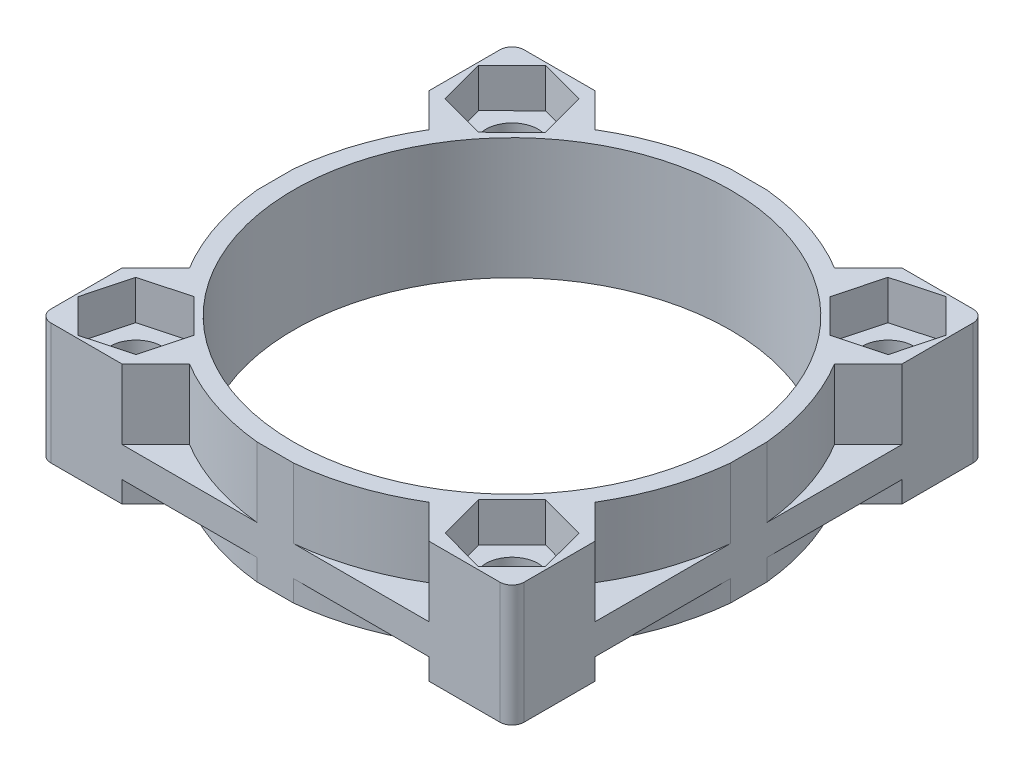
SolidWorks part; units mm, degrees
ref_plane "Front Plane" through (0, 0, 0) normal (0, 0, 1) x (1, 0, 0)
ref_plane "Top Plane" through (0, 0, 0) normal (0, 1, 0) x (1, 0, 0)
ref_plane "Right Plane" through (0, 0, 0) normal (1, 0, 0) x (0, 0, -1)
ref_plane "Plane1" through (0, 35.3803, 0) normal (0, -1, 0) x (1, 0, 0)
sketch "Sketch1" plane through (0, 35.3803, 0) normal (0, -1, 0) x (1, 0, 0)
  line L0 (498.5578, 781.9917) -> (537.5578, 781.9917)
  line L1 (537.5578, 781.9917) -> (537.5578, 820.9917)
  line L2 (537.5578, 820.9917) -> (498.5578, 820.9917)
  line L3 (498.5578, 820.9917) -> (498.5578, 781.9917)
extrude "Boss-Extrude1" add sketch "Sketch1" against normal blind 10
sketch "Sketch2" plane through (0, 45.3803, 0) normal (0, 1, 0) x (-1, 0, 0)
  line L0 (-505.3955, 781.9917) -> (-508.1811, 784.7774)
  line L1 (-516.5553, 781.9917) -> (-505.3955, 781.9917)
  arc A0 (-508.1811, 784.7774) -> (-516.5553, 781.9917) centre (-518.5578, 801.9917) cw
extrude "Cut-Extrude1" cut sketch "Sketch2" against normal blind 5.75
sketch "Sketch3" plane through (0, 35.3803, 0) normal (0, -1, 0) x (1, 0, 0)
  line L0 (508.1811, 784.7774) -> (505.3955, 781.9917)
  line L1 (505.3955, 781.9917) -> (516.5553, 781.9917)
  arc A0 (516.5553, 781.9917) -> (508.1811, 784.7774) centre (518.5578, 801.9917) cw
extrude "Cut-Extrude2" cut sketch "Sketch3" against normal blind 1.75
sketch "Sketch4" plane through (0, 35.3803, 0) normal (0, -1, 0) x (1, 0, 0)
  line L0 (530.7201, 781.9917) -> (527.9344, 784.7774)
  line L1 (519.5603, 781.9917) -> (530.7201, 781.9917)
  arc A0 (527.9344, 784.7774) -> (519.5603, 781.9917) centre (517.5578, 801.9917) cw
extrude "Cut-Extrude3" cut sketch "Sketch4" against normal blind 1.75
sketch "Sketch5" plane through (0, 45.3803, 0) normal (0, 1, 0) x (-1, 0, 0)
  line L0 (-527.9344, 784.7774) -> (-530.7201, 781.9917)
  line L1 (-530.7201, 781.9917) -> (-519.5603, 781.9917)
  arc A0 (-519.5603, 781.9917) -> (-527.9344, 784.7774) centre (-517.5578, 801.9917) cw
extrude "Cut-Extrude4" cut sketch "Sketch5" against normal blind 5.75
sketch "Sketch6" plane through (0, 35.3803, 0) normal (0, -1, 0) x (1, 0, 0)
  line L0 (498.5578, 788.8295) -> (501.3434, 791.6151)
  line L1 (498.5578, 799.9892) -> (498.5578, 788.8295)
  arc A0 (501.3434, 791.6151) -> (498.5578, 799.9892) centre (518.5578, 801.9917) cw
extrude "Cut-Extrude5" cut sketch "Sketch6" against normal blind 1.75
sketch "Sketch7" plane through (0, 45.3803, 0) normal (0, 1, 0) x (-1, 0, 0)
  line L0 (-501.3434, 791.6151) -> (-498.5578, 788.8295)
  line L1 (-498.5578, 788.8295) -> (-498.5578, 799.9892)
  arc A0 (-498.5578, 799.9892) -> (-501.3434, 791.6151) centre (-518.5578, 801.9917) cw
extrude "Cut-Extrude6" cut sketch "Sketch7" against normal blind 5.75
sketch "Sketch8" plane through (0, 45.3803, 0) normal (0, 1, 0) x (-1, 0, 0)
  line L0 (-498.5578, 814.154) -> (-501.3305, 811.3471)
  line L1 (-498.5578, 802.9942) -> (-498.5578, 814.154)
  arc A0 (-501.3305, 811.3471) -> (-498.5578, 802.9942) centre (-518.5578, 800.9917) cw
extrude "Cut-Extrude7" cut sketch "Sketch8" against normal blind 5.75
sketch "Sketch9" plane through (0, 35.3803, 0) normal (0, -1, 0) x (1, 0, 0)
  line L0 (501.3305, 811.3471) -> (498.5578, 814.154)
  line L1 (498.5578, 814.154) -> (498.5578, 802.9942)
  arc A0 (498.5578, 802.9942) -> (501.3305, 811.3471) centre (518.5578, 800.9917) cw
extrude "Cut-Extrude8" cut sketch "Sketch9" against normal blind 1.75
sketch "Sketch10" plane through (0, 35.3803, 0) normal (0, -1, 0) x (1, 0, 0)
  line L0 (505.3955, 820.9917) -> (508.1811, 818.2061)
  line L1 (516.5553, 820.9917) -> (505.3955, 820.9917)
  arc A0 (508.1811, 818.2061) -> (516.5553, 820.9917) centre (518.5578, 800.9917) cw
extrude "Cut-Extrude9" cut sketch "Sketch10" against normal blind 1.75
sketch "Sketch11" plane through (0, 45.3803, 0) normal (0, 1, 0) x (-1, 0, 0)
  line L0 (-508.1811, 818.2061) -> (-505.3955, 820.9917)
  line L1 (-505.3955, 820.9917) -> (-516.5553, 820.9917)
  arc A0 (-516.5553, 820.9917) -> (-508.1811, 818.2061) centre (-518.5578, 800.9917) cw
extrude "Cut-Extrude10" cut sketch "Sketch11" against normal blind 5.75
sketch "Sketch12" plane through (0, 45.3803, 0) normal (0, 1, 0) x (-1, 0, 0)
  line L0 (-530.7201, 820.9917) -> (-527.9344, 818.2061)
  line L1 (-519.5603, 820.9917) -> (-530.7201, 820.9917)
  arc A0 (-527.9344, 818.2061) -> (-519.5603, 820.9917) centre (-517.5578, 800.9917) cw
extrude "Cut-Extrude11" cut sketch "Sketch12" against normal blind 5.75
sketch "Sketch13" plane through (0, 35.3803, 0) normal (0, -1, 0) x (1, 0, 0)
  line L0 (527.9344, 818.2061) -> (530.7201, 820.9917)
  line L1 (530.7201, 820.9917) -> (519.5603, 820.9917)
  arc A0 (519.5603, 820.9917) -> (527.9344, 818.2061) centre (517.5578, 800.9917) cw
extrude "Cut-Extrude12" cut sketch "Sketch13" against normal blind 1.75
sketch "Sketch14" plane through (0, 45.3803, 0) normal (0, 1, 0) x (-1, 0, 0)
  line L0 (-537.5578, 788.8295) -> (-534.7722, 791.6151)
  line L1 (-537.5578, 799.9892) -> (-537.5578, 788.8295)
  arc A0 (-534.7722, 791.6151) -> (-537.5578, 799.9892) centre (-517.5578, 801.9917) cw
extrude "Cut-Extrude13" cut sketch "Sketch14" against normal blind 5.75
sketch "Sketch15" plane through (0, 35.3803, 0) normal (0, -1, 0) x (1, 0, 0)
  line L0 (534.7722, 791.6151) -> (537.5578, 788.8295)
  line L1 (537.5578, 788.8295) -> (537.5578, 799.9892)
  arc A0 (537.5578, 799.9892) -> (534.7722, 791.6151) centre (517.5578, 801.9917) cw
extrude "Cut-Extrude14" cut sketch "Sketch15" against normal blind 1.75
sketch "Sketch16" plane through (0, 35.3803, 0) normal (0, -1, 0) x (1, 0, 0)
  line L0 (537.5578, 814.154) -> (534.7722, 811.3684)
  line L1 (537.5578, 802.9942) -> (537.5578, 814.154)
  arc A0 (534.7722, 811.3684) -> (537.5578, 802.9942) centre (517.5578, 800.9917) cw
extrude "Cut-Extrude15" cut sketch "Sketch16" against normal blind 1.75
sketch "Sketch17" plane through (0, 45.3803, 0) normal (0, 1, 0) x (-1, 0, 0)
  line L0 (-534.7722, 811.3684) -> (-537.5578, 814.154)
  line L1 (-537.5578, 814.154) -> (-537.5578, 802.9942)
  arc A0 (-537.5578, 802.9942) -> (-534.7722, 811.3684) centre (-517.5578, 800.9917) cw
extrude "Cut-Extrude16" cut sketch "Sketch17" against normal blind 5.75
sketch "Sketch18" plane through (0, 35.3803, 0) normal (0, -1, 0) x (1, 0, 0)
  line L0 (536.3236, 814.2406) -> (537.3232, 818.0115)
  line L1 (537.3232, 818.0115) -> (534.5574, 820.7626)
  line L2 (534.5574, 820.7626) -> (530.7919, 819.7429)
  line L3 (530.7919, 819.7429) -> (529.7923, 815.972)
  line L4 (529.7923, 815.972) -> (532.5582, 813.2209)
  line L5 (532.5582, 813.2209) -> (536.3236, 814.2406)
extrude "Cut-Extrude17" cut sketch "Sketch18" against normal blind 2.21
sketch "Sketch19" plane through (0, 35.3803, 0) normal (0, -1, 0) x (1, 0, 0)
  line L0 (498.7923, 818.0115) -> (499.7919, 814.2406)
  line L1 (499.7919, 814.2406) -> (503.5574, 813.2209)
  line L2 (503.5574, 813.2209) -> (506.3232, 815.972)
  line L3 (506.3232, 815.972) -> (505.3236, 819.7429)
  line L4 (505.3236, 819.7429) -> (501.5582, 820.7626)
  line L5 (501.5582, 820.7626) -> (498.7923, 818.0115)
extrude "Cut-Extrude18" cut sketch "Sketch19" against normal blind 2.21
sketch "Sketch20" plane through (0, 35.3803, 0) normal (0, -1, 0) x (1, 0, 0)
  line L0 (499.7919, 788.7429) -> (498.7923, 784.972)
  line L1 (498.7923, 784.972) -> (501.5582, 782.2209)
  line L2 (501.5582, 782.2209) -> (505.3236, 783.2406)
  line L3 (505.3236, 783.2406) -> (506.3232, 787.0115)
  line L4 (506.3232, 787.0115) -> (503.5574, 789.7626)
  line L5 (503.5574, 789.7626) -> (499.7919, 788.7429)
extrude "Cut-Extrude19" cut sketch "Sketch20" against normal blind 2.21
sketch "Sketch21" plane through (0, 35.3803, 0) normal (0, -1, 0) x (1, 0, 0)
  line L0 (537.3232, 784.972) -> (536.3236, 788.7429)
  line L1 (536.3236, 788.7429) -> (532.5582, 789.7626)
  line L2 (532.5582, 789.7626) -> (529.7923, 787.0115)
  line L3 (529.7923, 787.0115) -> (530.7919, 783.2406)
  line L4 (530.7919, 783.2406) -> (534.5574, 782.2209)
  line L5 (534.5574, 782.2209) -> (537.3232, 784.972)
extrude "Cut-Extrude20" cut sketch "Sketch21" against normal blind 2.21
sketch "Sketch22" plane through (0, 45.3803, 0) normal (0, 1, 0) x (-1, 0, 0)
  line L0 (-529.7923, 787.0115) -> (-532.5582, 789.7626)
  line L1 (-532.5582, 789.7626) -> (-536.3236, 788.7429)
  line L2 (-536.3236, 788.7429) -> (-537.3232, 784.972)
  line L3 (-537.3232, 784.972) -> (-534.5574, 782.2209)
  line L4 (-534.5574, 782.2209) -> (-530.7919, 783.2406)
  line L5 (-530.7919, 783.2406) -> (-529.7923, 787.0115)
extrude "Cut-Extrude21" cut sketch "Sketch22" against normal blind 3.24
sketch "Sketch23" plane through (0, 45.3803, 0) normal (0, 1, 0) x (-1, 0, 0)
  line L0 (-503.5574, 789.7626) -> (-506.3232, 787.0115)
  line L1 (-506.3232, 787.0115) -> (-505.3236, 783.2406)
  line L2 (-505.3236, 783.2406) -> (-501.5582, 782.2209)
  line L3 (-501.5582, 782.2209) -> (-498.7923, 784.972)
  line L4 (-498.7923, 784.972) -> (-499.7919, 788.7429)
  line L5 (-499.7919, 788.7429) -> (-503.5574, 789.7626)
extrude "Cut-Extrude22" cut sketch "Sketch23" against normal blind 3.24
sketch "Sketch24" plane through (0, 45.3803, 0) normal (0, 1, 0) x (-1, 0, 0)
  line L0 (-506.3232, 815.972) -> (-503.5574, 813.2209)
  line L1 (-503.5574, 813.2209) -> (-499.7919, 814.2406)
  line L2 (-499.7919, 814.2406) -> (-498.7923, 818.0115)
  line L3 (-498.7923, 818.0115) -> (-501.5582, 820.7626)
  line L4 (-501.5582, 820.7626) -> (-505.3236, 819.7429)
  line L5 (-505.3236, 819.7429) -> (-506.3232, 815.972)
extrude "Cut-Extrude23" cut sketch "Sketch24" against normal blind 3.24
sketch "Sketch25" plane through (0, 45.3803, 0) normal (0, 1, 0) x (-1, 0, 0)
  line L0 (-532.5582, 813.2209) -> (-529.7923, 815.972)
  line L1 (-529.7923, 815.972) -> (-530.7919, 819.7429)
  line L2 (-530.7919, 819.7429) -> (-534.5574, 820.7626)
  line L3 (-534.5574, 820.7626) -> (-537.3232, 818.0115)
  line L4 (-537.3232, 818.0115) -> (-536.3236, 814.2406)
  line L5 (-536.3236, 814.2406) -> (-532.5582, 813.2209)
extrude "Cut-Extrude24" cut sketch "Sketch25" against normal blind 3.24
hole_wizard "M33 Clearance Hole1" positions "Sketch27" profile "Sketch26" hole size "M33" standard "ANSI Metric"
sketch "Sketch27" plane through (0, 35.3803, 0) normal (0, -1, 0) x (-1, 0, 0)
  point P0 (-518.0578, -801.4917)
sketch "Sketch26" plane through (518.0578, 35.3803, 801.4917) normal (1, 0, 0) x (0, 0, -1)
  line L0 (0, 0) -> (0, 10)
  line L1 (0, 10) -> (18, 10)
  line L2 (18, 10) -> (18, 0)
  line L5 (18, 0) -> (0, 0)
  line L11 (0, -6.35) -> (0, 107.95) construction
  dimension "Thru Hole Dia." = 36
  dimension "Thru Hole Depth" = 10
hole_wizard "Ø4.3 (4.3) Diameter Hole1" positions "Sketch29" profile "Sketch28" hole size "Ø4.3" standard "ANSI Metric"
sketch "Sketch29" plane through (0, 37.5903, 0) normal (0, -1, 0) x (-1, 0, 0)
  point P0 (-533.5578, -785.9917)
  point P1 (-502.5578, -785.9917)
  point P2 (-502.5578, -816.9917)
  point P3 (-533.5578, -816.9917)
sketch "Sketch28" plane through (533.5578, 37.5903, 785.9917) normal (1, 0, 0) x (0, 0, -1)
  line L0 (0, 0) -> (0, 7.79)
  line L1 (0, 7.79) -> (2.15, 7.79)
  line L2 (2.15, 7.79) -> (2.15, 0)
  line L5 (2.15, 0) -> (0, 0)
  line L11 (0, -6.35) -> (0, 107.95) construction
  dimension "Thru Hole Dia." = 4.3
  dimension "Thru Hole Depth" = 7.79
fillet "Fillet1" radius 1 4 edges at (498.5578, 40.3803, 820.9917) (537.5578, 40.3803, 820.9917) (537.5578, 40.3803, 781.9917) (498.5578, 40.3803, 781.9917) tangent propagation no
